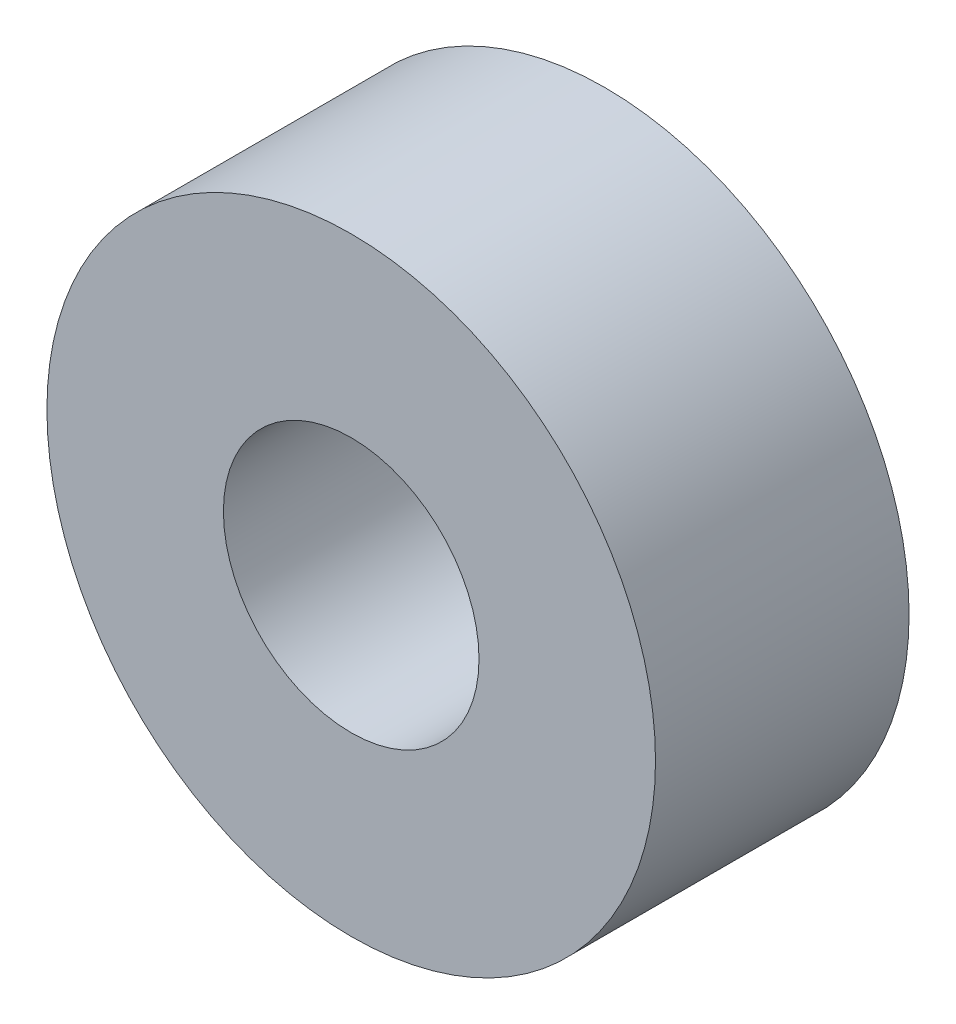
SolidWorks part; units mm, degrees
ref_plane "Front Plane" through (0, 0, 0) normal (0, 0, 1) x (1, 0, 0)
ref_plane "Top Plane" through (0, 0, 0) normal (0, 1, 0) x (1, 0, 0)
ref_plane "Right Plane" through (0, 0, 0) normal (1, 0, 0) x (0, 0, -1)
sketch "Sketch1" plane through (0, 0, 0) normal (1, 0, 0) x (0, 0, -1)
  line L0 (-3.9688, -4.0005) -> (-3.9688, 4.0005) construction
  line L1 (3.9688, -9.525) -> (-3.9688, -9.525) construction
  line L2 (3.9688, -9.525) -> (3.9688, 9.525) construction
  line L3 (3.9688, 9.525) -> (-3.9688, 9.525) construction
  line L4 (-3.9688, -9.525) -> (-3.9688, 9.525) construction
  line L5 (0, 9.525) -> (0, -9.525) construction
  line L6 (3.9688, 0) -> (-3.9688, 0) construction
  point P0 (0, 0)
  point P7 (-3.9688, 0)
  dimension "D1" = 8.001
  dimension "D2" = 19.05
sketch "Sketch3" plane through (0, 0, 0) normal (0, 0, 1) x (1, 0, 0)
  circle A0 centre (0, 0) radius 4.0005 construction
  circle A1 centre (0, 0) radius 9.525 construction
  point P6 (0, -4.0005)
  dimension "OD" = 19.05
  dimension "ID" = 8.001
sketch "Sketch2" plane through (0, 0, 0) normal (0, 0, 1) x (1, 0, 0)
  circle A0 centre (0, 0) radius 9.525
  circle A1 centre (0, 0) radius 4.0005
extrude "Extrude1" add sketch "Sketch2" along normal up to vertex and the other way up to vertex up to point (0, -9.525, 3.9688) other way up to point (0, 9.525, -3.9688)
equation "\"D1@Sketch1\"=\"ID@Sketch3\""
equation "\"D2@Sketch1\"=\"OD@Sketch3\""
